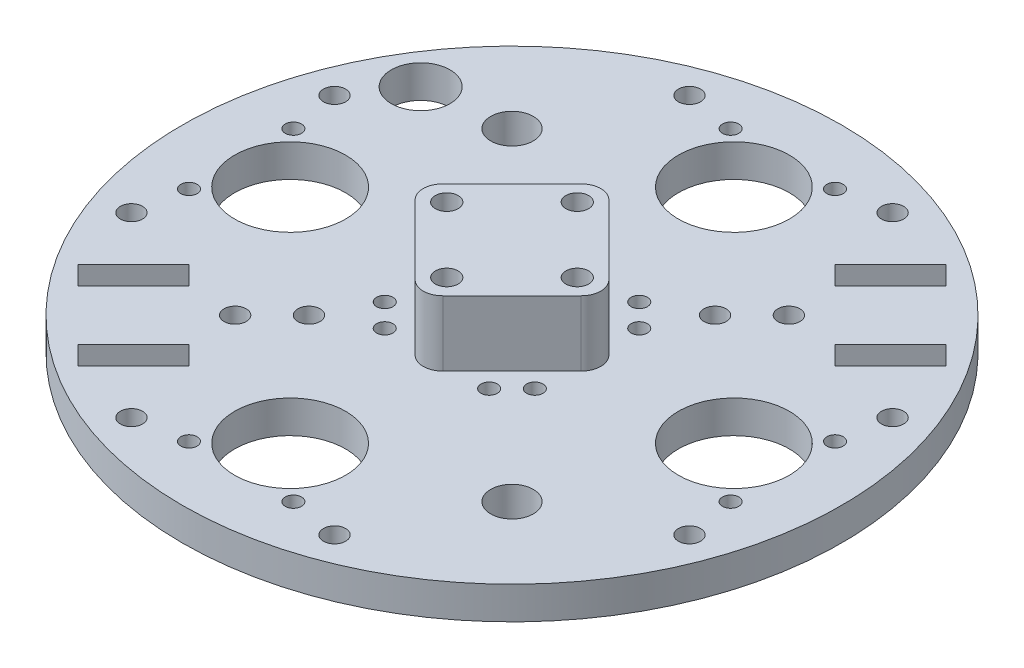
SolidWorks part; units mm, degrees
ref_plane "Front Plane" through (0, 0, 0) normal (0, 0, 1) x (1, 0, 0)
ref_plane "Top Plane" through (0, 0, 0) normal (0, 1, 0) x (1, 0, 0)
ref_plane "Right Plane" through (0, 0, 0) normal (1, 0, 0) x (0, 0, -1)
ref_axis "Axis1" through (0, 15.75, 0) along (0, -1, 0)
sketch "Sketch1" plane through (0, 0, 0) normal (0, 1, 0) x (1, 0, 0)
  circle A0 centre (0, 0) radius 50.5
  dimension "D1" = 101
extrude "Boss-Extrude1" add sketch "Sketch1" along normal blind 5
sketch "Sketch2" plane through (0, 5, 0) normal (0, 1, 0) x (1, 0, 0)
  line L5 (0, 0) -> (34, 0) construction
  line L6 (41.5, -8) -> (41.5, 8) construction
  line L10 (41.5, -8) -> (11.5, -8) construction
  line L11 (41.5, 8) -> (11.5, 8) construction
  line L12 (11.5, -8) -> (11.5, 8) construction
  line L13 (11.5, 0) -> (41.5, 0) construction
  circle A20 centre (34, 0) radius 8.5
  circle A21 centre (41.5, -8) radius 1.25
  circle A22 centre (41.5, 8) radius 1.25
  circle A23 centre (11.5, 8) radius 1.25
  circle A24 centre (11.5, -8) radius 1.25
  point P36 (0, 0)
  dimension "D1" = 16
  dimension "D5" = 34
  dimension "D2" = 17
  dimension "D6" = 2.5
  dimension "D3" = 7.5
  dimension "D4" = 30
  dimension "D7" = 180
extrude "Cut-Extrude1" cut sketch "Sketch2" against normal through all
pattern_circular "CirPattern1" count 4 over 360 about axis through (0, 5, 0) along (0, -1, 0) of "Cut-Extrude1"
sketch "Sketch3" plane through (0, 5, 0) normal (0, 1, 0) x (1, 0, 0)
  line L0 (0, 0) -> (10, 0) construction
  line L1 (0, -14.8492) -> (14.8492, 0)
  line L2 (0, -14.8492) -> (-14.8492, 0)
  line L3 (14.8492, 0) -> (0, 14.8492)
  line L4 (-14.8492, 0) -> (0, 14.8492)
  line L5 (0, -14.8492) -> (0, 14.8492) construction
  line L6 (14.8492, 0) -> (-14.8492, 0) construction
  line L7 (0, 0) -> (50.5, 0) construction
  circle A0 centre (10, 0) radius 1.75
  circle A2 centre (0, -10) radius 1.75
  circle A3 centre (-10, 0) radius 1.75
  circle A4 centre (0, 10) radius 1.75
  circle A5 centre (0, 0) radius 50.5 construction
  point P13 (0, 0)
  dimension "D2" = 3.5
  dimension "D3" = 4
  dimension "D1" = 10
  dimension "D4" = 45
  dimension "D5" = 21
  dimension "D6" = 21
extrude "Boss-Extrude2" add sketch "Sketch3" along normal blind 10
fillet "Fillet2" radius 3 4 edges at (-14.8492, 10, 0) (0, 10, -14.8492) (14.8492, 10, 0) (0, 10, 14.8492)
sketch "Sketch4" plane through (0, 5, 0) normal (0, 1, 0) x (1, 0, 0)
  line L0 (-35.7089, -35.7089) -> (35.7089, 35.7089) construction
  line L1 (0, 0) -> (50.5, 0) construction
  line L2 (0, 0) -> (-35.7089, 35.7089) construction
  line L7 (20.8597, 28.6378) -> (29.3449, 37.1231)
  line L8 (20.8597, 28.6378) -> (18.0312, 31.4663)
  line L9 (29.3449, 37.1231) -> (26.5165, 39.9515)
  line L10 (18.0312, 31.4663) -> (26.5165, 39.9515)
  line L11 (20.8597, 28.6378) -> (26.5165, 39.9515) construction
  line L12 (29.3449, 37.1231) -> (18.0312, 31.4663) construction
  line L13 (31.4663, 18.0312) -> (39.9515, 26.5165)
  line L14 (31.4663, 18.0312) -> (28.6378, 20.8597)
  line L15 (39.9515, 26.5165) -> (37.1231, 29.3449)
  line L16 (28.6378, 20.8597) -> (37.1231, 29.3449)
  line L17 (31.4663, 18.0312) -> (37.1231, 29.3449) construction
  line L18 (39.9515, 26.5165) -> (28.6378, 20.8597) construction
  line L19 (34.2947, 23.6881) -> (23.6881, 34.2947) construction
  line L20 (-26.5165, -39.9515) -> (-29.3449, -37.1231)
  line L21 (-20.8597, -28.6378) -> (-29.3449, -37.1231)
  line L22 (-18.0312, -31.4663) -> (-20.8597, -28.6378)
  line L23 (-18.0312, -31.4663) -> (-26.5165, -39.9515)
  line L24 (-37.1231, -29.3449) -> (-39.9515, -26.5165)
  line L25 (-31.4663, -18.0312) -> (-39.9515, -26.5165)
  line L26 (-28.6378, -20.8597) -> (-31.4663, -18.0312)
  line L27 (-28.6378, -20.8597) -> (-37.1231, -29.3449)
  circle A0 centre (0, 0) radius 50.5 construction
  circle A2 centre (21.2132, 21.2132) radius 1.7
  circle A4 centre (-21.2132, -21.2132) radius 1.7
  circle A5 centre (-24.7487, 24.7487) radius 3.2639
  circle A6 centre (24.7487, -24.7487) radius 3.2639
  circle A7 centre (15.5563, 15.5563) radius 1.7
  circle A8 centre (-15.5563, -15.5563) radius 1.7
  point P4 (0, 0)
  point P10 (23.6881, 34.2947)
  point P11 (34.2947, 23.6881)
  point P22 (28.9914, 28.9914)
  dimension "D5" = 3.4
  dimension "D6" = 11
  dimension "D8" = 6.5278
  dimension "D9" = 35
  dimension "D10" = 8
  dimension "D1" = 45
  dimension "D2" = 12
  dimension "D3" = 4
  dimension "D4" = 11
  dimension "D7" = 41
extrude "Cut-Extrude2" cut sketch "Sketch4" against normal through all
draft "Draft1" [suppressed] draft angle 10 parameters "D1"=10
sketch "Sketch6" plane through (0, 0, 0) normal (0, 1, 0) x (1, 0, 0)
  line L0 (0, 0) -> (0, 50.5) construction
  line L1 (0, 0) -> (-19.3255, 46.6559) construction
  line L2 (0, 0) -> (-17.9861, 43.4223) construction
  line L3 (0, 0) -> (43.4223, 17.9861) construction
  circle A0 centre (0, 0) radius 50.5 construction
  circle A1 centre (-17.9861, 43.4223) radius 1.7
  circle A2 centre (43.4223, 17.9861) radius 1.7
  circle A3 centre (17.9861, -43.4223) radius 1.7
  circle A4 centre (-43.4223, -17.9861) radius 1.7
  dimension "D2" = 3.4
  dimension "D1" = 22.5
  dimension "D5" = 90
  dimension "D6" = 47
  dimension "D4" = 4
extrude "Cut-Extrude7" [suppressed] cut sketch "Sketch6" along normal through all
sketch "Sketch7" plane through (0, 0, 0) normal (0, 1, 0) x (1, 0, 0)
  line L0 (0, 0) -> (0, 59.9952) construction
  line L1 (0, 0) -> (-37.3141, 23.3164) construction
  circle A0 centre (-37.3141, 23.3164) radius 4.5
  dimension "D1" = 9
  dimension "D2" = 44
  dimension "D3" = 58
extrude "Cut-Extrude9" cut sketch "Sketch7" along normal through all
sketch "Sketch8" plane through (0, 0, 0) normal (0, 1, 0) x (1, 0, 0)
  line L0 (0, 0) -> (0, 50.5) construction
  line L1 (-15.5619, 42.756) -> (0, 0) construction
  line L2 (15.5619, 42.756) -> (0, 0) construction
  circle A0 centre (0, 0) radius 50.5 construction
  circle A1 centre (0, 0) radius 45.5 construction
  circle A2 centre (-15.5619, 42.756) radius 1.7
  circle A3 centre (15.5619, 42.756) radius 1.7
  dimension "D1" = 3.4
  dimension "D2" = 40
  dimension "D3" = 91
extrude "Cut-Extrude10" cut sketch "Sketch8" along normal through all
pattern_circular "CirPattern2" count 4 over 360 about axis through (0, 15.75, 0) along (0, -1, 0) of "Cut-Extrude10"
